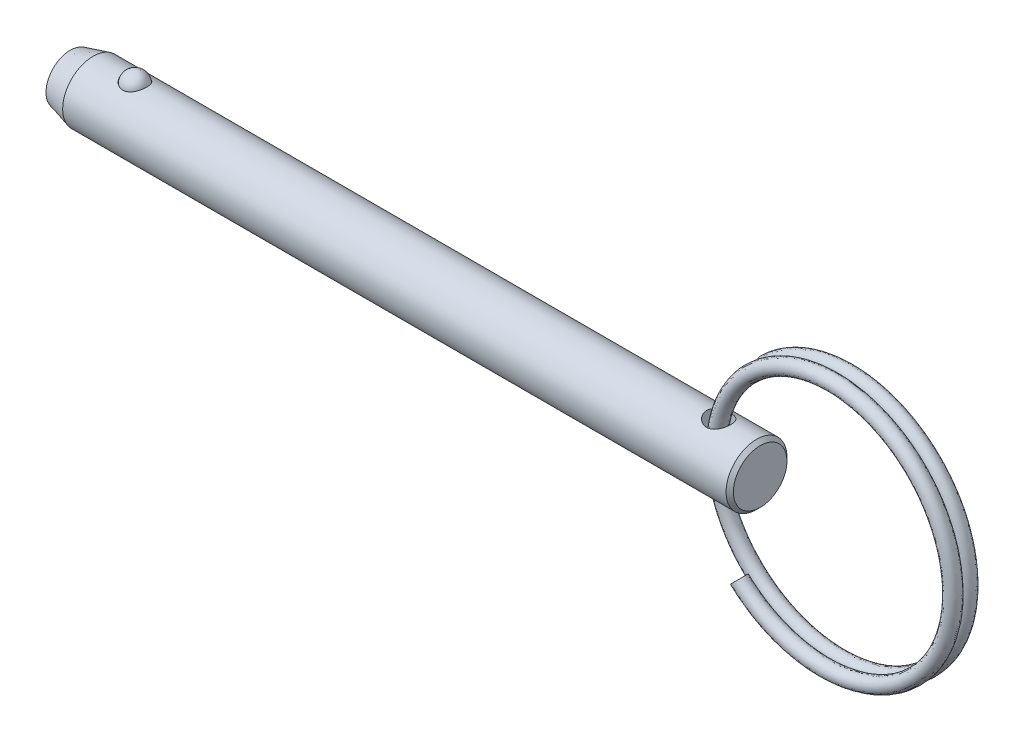
SolidWorks part; units mm, degrees
material "Plain Carbon Steel"
ref_plane "Front" through (0, 0, 0) normal (0, 0, 1) x (1, 0, 0)
ref_plane "Top" through (0, 0, 0) normal (0, 1, 0) x (1, 0, 0)
ref_plane "Right" through (0, 0, 0) normal (1, 0, 0) x (0, 0, -1)
sketch "Sketch1" plane through (0, 0, 0) normal (0, 0, 1) x (1, 0, 0)
  line L0 (35.9664, 2.794) -> (35.5854, 3.175)
  line L1 (35.5854, 3.175) -> (35.9664, 3.175) construction
  line L4 (35.9664, 2.794) -> (35.9664, 0)
  line L5 (35.9664, 3.175) -> (35.9664, 2.794) construction
  line L16 (35.5854, 3.175) -> (-33.5965, 3.175)
  line L17 (-35.9664, 3.175) -> (-35.9664, 2.54) construction
  line L19 (-33.5965, 3.175) -> (-35.9664, 3.175) construction
  line L22 (-35.9664, -3.175) -> (-33.5965, -3.175) construction
  line L23 (-29.2319, 2.8575) -> (-29.2319, -2.8575) construction
  line L24 (-35.9664, 0) -> (35.9664, 0)
  line L27 (35.9664, 0) -> (38.7604, 0) construction
  line L29 (-35.9664, 0) -> (-35.9664, -2.54) construction
  line L36 (30.3784, 0) -> (30.3784, 3.175) construction
  line L37 (-35.9664, 2.54) -> (-35.9664, 0)
  line L38 (-33.5965, -3.175) -> (35.9664, -3.175) construction
  line L39 (-35.9664, -2.54) -> (-35.9664, -3.175) construction
  line L40 (-33.5965, 3.175) -> (-35.9664, 2.54)
  line L42 (-33.5965, -3.175) -> (-35.9664, -2.54) construction
  line L43 (-33.5965, 3.175) -> (-33.5965, -3.175) construction
  circle A2 centre (-29.2319, 2.8575) radius 1.2319 construction
  point P35 (-28.0416, 3.175)
  dimension "A1" = 15
revolve "Revolve1" add sketch "Sketch1" angle 360 about L27
sketch "Sketch2" plane through (0, 0, 0) normal (0, 0, 1) x (1, 0, 0)
  line L0 (-27.9746, 2.8575) -> (-30.4892, 2.8575)
  line L1 (-29.2319, 4.0894) -> (-29.2319, 4.1148) construction
  line L2 (-27.9746, 2.8575) -> (-25.46, 2.8575) construction
  circle A0 centre (-29.2319, 2.8575) radius 1.2319 construction
  circle A1 centre (-29.2319, 2.8575) radius 1.2319 construction
  arc A2 (-30.4892, 2.8575) -> (-27.9746, 2.8575) centre (-29.2319, 2.8575) cw
  dimension "D1" = 0.0254
revolve "Cut-Revolve1" cut sketch "Sketch2" angle 360 about L2
sketch "Sketch3" plane through (0, 0, 0) normal (0, 0, 1) x (1, 0, 0)
  line L0 (-28, 2.8575) -> (-30.4638, 2.8575)
  line L1 (-28, 2.8575) -> (-25.5362, 2.8575) construction
  circle A0 centre (-29.2319, 2.8575) radius 1.2319 construction
  arc A1 (-28, 2.8575) -> (-30.4638, 2.8575) centre (-29.2319, 2.8575) ccw
revolve "Revolve2" add sketch "Sketch3" angle 360 about L1
sketch "Sketch4" plane through (0, 0, 0) normal (0, 0, 1) x (1, 0, 0)
  line L1 (31.6484, -3.175) -> (32.9184, -3.175)
  line L2 (31.6484, -3.175) -> (31.6484, 3.175)
  line L3 (31.6484, 3.175) -> (32.9184, 3.175)
  line L4 (32.9184, -3.175) -> (32.9184, 3.175)
  line L5 (31.6484, -3.175) -> (31.6484, -4.445) construction
  line L6 (32.9184, 3.175) -> (35.9664, 3.175) construction
  line L8 (30.3784, -3.175) -> (30.3784, 3.175) construction
  line L9 (30.3784, 0) -> (31.6484, 0) construction
  line L11 (31.6484, 0) -> (32.9184, 0) construction
  line L12 (35.5854, 3.175) -> (-33.5965, 3.175) construction
  line L14 (-33.5965, -3.175) -> (35.9664, -3.175) construction
  dimension "D1" = 2.54
revolve "Cut-Revolve2" cut sketch "Sketch4" angle 360 about L2
sketch "Sketch5" plane through (0, 0, 0) normal (0, 0, 1) x (1, 0, 0)
  line L0 (0, 0) -> (30.6714, 0) construction
  line L1 (30.6714, 0) -> (30.6714, 3.175) construction
  line L2 (35.5854, 3.175) -> (-33.5965, 3.175) construction
  line L3 (44.1334, 0) -> (57.5954, 0) construction
  line L4 (32.9184, 3.175) -> (32.6254, 3.175) construction
  line L5 (31.6484, 3.175) -> (32.9184, 3.175) construction
  line L6 (31.0512, 3.175) -> (31.0512, -3.175) construction
  line L7 (30.6714, 3.175) -> (30.3784, 3.175) construction
  line L8 (31.6484, -3.175) -> (32.9184, -3.175) construction
  line L9 (31.0512, -3.175) -> (32.9184, -3.175) construction
  line L10 (30.6714, 0) -> (44.1334, 0) construction
  line L12 (32.6254, 3.175) -> (31.0512, 3.175) construction
  line L13 (44.1334, 11.938) -> (44.1334, 13.462) construction
  circle A0 centre (44.1334, 0) radius 13.462
  circle A1 centre (44.1334, 0) radius 11.938 construction
  circle A2 centre (44.1334, 0) radius 12.7 construction
  point P26 (44.1334, 12.7)
curve "Helix/Spiral1" pitch 1.5494 height 1.3557 radius 13.462 left hand yes centre (44.1334, 0, 0) axis (0, 0, -1) start towards (1, 0, 0)
sketch "Sketch6" plane through (114.0038, 0, 0) normal (0, 1, 0) x (0, 0, -1)
  line L0 (0, 81.8084) -> (0, 82.5704) construction
  line L1 (0, 82.5704) -> (0, 83.3324) construction
  circle A0 centre (0, 82.5704) radius 0.762
  dimension "D1" = 1.524
sketch "Sketch7" plane through (0, 0, 0) normal (0, 0, 1) x (1, 0, 0)
  circle A0 centre (44.1334, 0) radius 13.462 construction
  circle A1 centre (44.1334, 0) radius 13.462
curve "Helix/Spiral2" pitch 1.5494 height 1.3557 radius 13.462 left hand yes centre (44.1334, 0, 0) axis (0, 0, 1) start towards (1, 0, 0)
sweep "Sweep1" add profiles "Sketch6" path "Helix/Spiral1"
sweep "Sweep2" add profiles "Sketch6<2>" path "Helix/Spiral2"
sketch "Sketch6<2>" plane through (114.0038, 0, 0) normal (0, 1, 0) x (0, 0, -1) same geometry as "Sketch6"
equation "\"D12@Sketch1\"=\"A@Sketch1\" * 0.80"
equation "\"D2@Sketch1\"=\"A@Sketch1\" * 0.9"
equation "\"D1@Sketch4\" = \"A@Sketch1\" / 2.5"
equation "\"Ring OD@Sketch5\" = \"R Ring Dia@Sketch5\" * 0.06"
equation "\"D4@Helix/Spiral1\"=\"Ring OD@Sketch5\" + 0.001"
equation "\"D1@Sketch6\"=\"Ring OD@Sketch5\""
equation "\"D4@Helix/Spiral2\" = \"D4@Helix/Spiral1\""
equation "\"D5@Helix/Spiral2\" = \"D5@Helix/Spiral1\""
